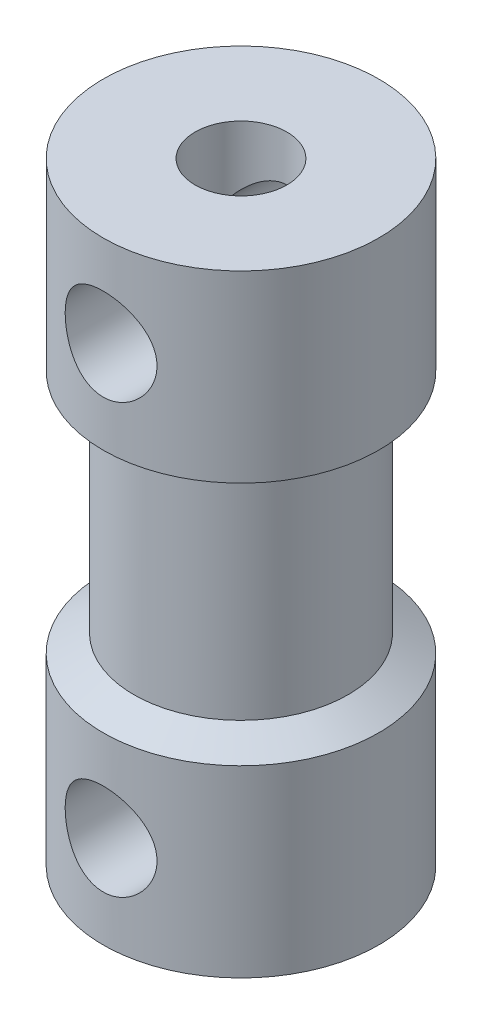
SolidWorks part; units mm, degrees
ref_plane "前基準面" through (0, 0, 0) normal (0, 0, 1) x (1, 0, 0)
ref_plane "上基準面" through (0, 0, 0) normal (0, 1, 0) x (1, 0, 0)
ref_plane "右基準面" through (0, 0, 0) normal (1, 0, 0) x (0, 0, -1)
sketch "草圖1" plane through (0, 0, 0) normal (0, 1, 0) x (1, 0, 0)
  circle A0 centre (0, 0) radius 3.5
  dimension "D1" = 7
extrude "填料-伸長1" add sketch "草圖1" along normal blind 20
sketch "草圖2" plane through (0, 20, 0) normal (0, 1, 0) x (1, 0, 0)
  circle A0 centre (0, 0) radius 1.5
  dimension "D1" = 3
extrude "除料-伸長1" cut sketch "草圖2" against normal blind 10
sketch "草圖3" plane through (0, 0, 0) normal (0, -1, 0) x (1, 0, 0)
  circle A0 centre (0, 0) radius 1
  dimension "D1" = 2
extrude "除料-伸長2" cut sketch "草圖3" against normal blind 10
sketch "草圖4" plane through (0, 0, 0) normal (0, -1, 0) x (1, 0, 0)
  circle A0 centre (0, 0) radius 4.5
  circle A1 centre (0, 0) radius 3.5
  dimension "D1" = 9
extrude "填料-伸長2" add sketch "草圖4" against normal blind 6
sketch "草圖5" plane through (0, 20, 0) normal (0, 1, 0) x (1, 0, 0)
  circle A0 centre (0, 0) radius 4.5
  circle A1 centre (0, 0) radius 3.5
extrude "填料-伸長3" add sketch "草圖5" against normal blind 6
chamfer "導角1" distance 0.58 angle 60 2 edges at (0, 14, 3.5) (0, 6, -3.5) first distance on face at (0, 6, -3.5)
sketch "草圖6" plane through (0, 0, 0) normal (0, 0, 1) x (1, 0, 0)
  line L0 (4.5, 20) -> (-4.5, 20) construction
  line L1 (-4.5, 0) -> (4.5, 0) construction
  circle A0 centre (0, 17) radius 1.5
  circle A1 centre (0, 3) radius 1.5
  dimension "D1" = 3
  dimension "D2" = 3
  dimension "D3" = 3
  dimension "D4" = 3
extrude "除料-伸長3" cut sketch "草圖6" against normal through all both and the other way through all
